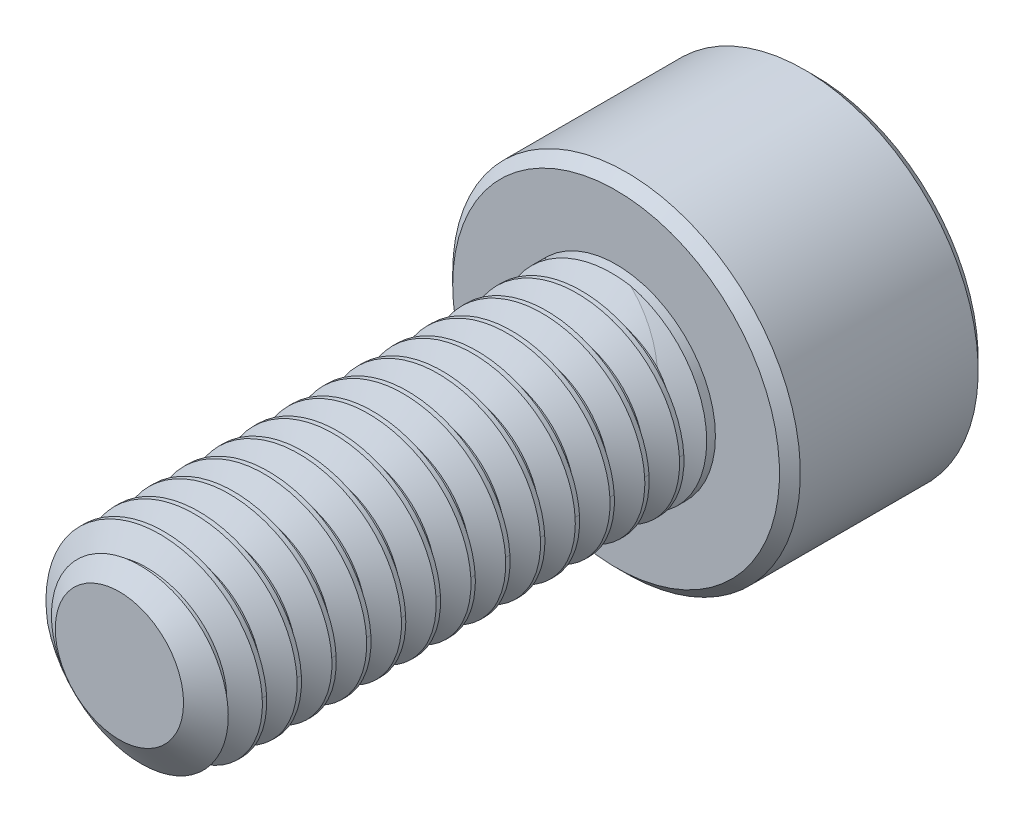
SolidWorks part; units mm, degrees
ref_plane "Front Plane" through (0, 0, 0) normal (0, 0, 1) x (1, 0, 0)
ref_plane "Top Plane" through (0, 0, 0) normal (0, 1, 0) x (1, 0, 0)
ref_plane "Right Plane" through (0, 0, 0) normal (1, 0, 0) x (0, 0, -1)
sketch "Sketch1" plane through (0, 0, 0) normal (0, 0, 1) x (1, 0, 0)
  circle A0 centre (0, 0) radius 2
  dimension "OD" = 4
extrude "Extrude1" add sketch "Sketch1" against normal blind 10
sketch "Sketch2" plane through (0, 0, 0) normal (0, 0, 1) x (1, 0, 0)
  circle A0 centre (0, 0) radius 2 construction
  circle A1 centre (0, 0) radius 2
curve "Helix/Spiral1" pitch 0.7 height 10.7 radius 2 centre (0, 0, 0) axis (0, 0, -1) start towards (0, 1, 0) parameters "pitch"=0.7
sketch "Sketch3" plane through (0, 0, 0) normal (1, 0, 0) x (0, 0, -1)
  line L0 (-0.6125, 2) -> (-0.35, 1.5453)
  line L1 (-0.35, 1.5453) -> (-0.2625, 1.5453)
  line L2 (-0.2625, 1.5453) -> (0, 2)
  line L3 (-0.6125, 2) -> (0, 2)
  line L4 (-0.3063, 2) -> (-0.3063, 1.5453) construction
  line L5 (-0.4813, 1.7727) -> (-0.1313, 1.7727) construction
  line L6 (0, 2) -> (0, -2) construction
  line L7 (0, -2) -> (10, -2) construction
  point P11 (3.15, -2)
  dimension "D1" = 0.0875
  dimension "D2" = 0.35
  dimension "D3" = 60
  dimension "D4" = 3.15
sweep "Cut-Sweep1" cut profiles "Sketch3" path "Helix/Spiral1"
sketch "Sketch4" plane through (0, 0, 0) normal (1, 0, 0) x (0, 0, -1)
  line L0 (0.4962, 2) -> (0, 1.2913)
  line L1 (0, 1.2913) -> (0, 2)
  line L2 (0.4962, 2) -> (0, 2)
  line L3 (-0.6125, 2) -> (0, 2) construction
  line L4 (0, 0) -> (7.0209, 0) construction
  dimension "D1" = 55
  dimension "D2" = 0.254
revolve "Cut-Revolve1" cut sketch "Sketch4" angle 360 about L4
sketch "Sketch5" plane through (0, 0, 0) normal (1, 0, 0) x (0, 0, -1)
  line L0 (10, 0.3311) -> (10, 1.814) construction
  line L1 (10, 2) -> (0.1203, 2)
  line L2 (10, 2) -> (10, 0)
  line L3 (10, 0) -> (0.0001, 0)
  line L4 (0.0001, 1.6698) -> (0.0001, 0)
  line L5 (0.1203, 2) -> (0.0001, 1.6698)
  line L6 (0, 0) -> (9.9695, 0) construction
  point P3 (0.0001, 2)
  point P10 (0.0001, 2)
  dimension "D1" = 0.3302
  dimension "Thread min" = 0.0001
  dimension "D3" = 20
revolve "partially thread" [suppressed] add sketch "Sketch5" angle 360 about L6
sketch "Sketch6" plane through (0, 0, -10) normal (0, 0, -1) x (-1, 0, 0)
  circle A0 centre (0, 0) radius 3.5
  dimension "head dia" = 7
extrude "Extrude2" add sketch "Sketch6" along normal blind 4
sketch "Sketch7" plane through (0, 0, -14) normal (0, 0, -1) x (-1, 0, 0)
  line L1 (0, 1.7321) -> (-1.5, 0.866)
  line L2 (-1.5, 0.866) -> (-1.5, -0.866)
  line L3 (-1.5, -0.866) -> (0, -1.7321)
  line L4 (0, -1.7321) -> (1.5, -0.866)
  line L5 (1.5, -0.866) -> (1.5, 0.866)
  line L6 (1.5, 0.866) -> (0, 1.7321)
  circle A0 centre (0, 0) radius 1.5 construction
  dimension "hex dia" = 3
extrude "Cut-Extrude1" cut sketch "Sketch7" against normal blind 2.25
sketch "Sketch8" plane through (0, 0, -14) normal (0, 0, -1) x (-1, 0, 0)
  circle A0 centre (0, 0) radius 1.7321
extrude "Cut-Extrude2" cut sketch "Sketch8" against normal through all draft 45
chamfer "Chamfer1" distance 0.21 angle 45 2 edges at (-3.5, 0, -14) (-3.5, 0, -10)
sketch "Sketch9" plane through (0, 0, 0) normal (1, 0, 0) x (0, 0, -1)
  line L0 (0, 2) -> (0, -2) construction
  line L1 (3.85, 2) -> (3.85, -2) construction
  dimension "D1" = 3.85
sketch "Sketch10" plane through (0, 0, 0) normal (1, 0, 0) x (0, 0, -1)
  line L0 (10, 2) -> (10, 0)
  line L1 (10, 2) -> (9.825, 2)
  line L2 (9.825, 2) -> (8.9966, 0)
  line L3 (10, 0) -> (8.9966, 0)
  line L4 (10, 3.29) -> (10, -3.29) construction
  dimension "D1" = 22.5
  dimension "D2" = 0.175
revolve "Revolve1" add sketch "Sketch10" angle 360 about L3
equation "\"D3@Helix/Spiral1\" = \"screw length@Extrude1\"+\"pitch@Helix/Spiral1\""
equation "\"D1@Sketch3\" = \"pitch@Helix/Spiral1\"*.125"
equation "\"D2@Sketch3\" = \"pitch@Helix/Spiral1\"*.5"
equation "\"D1@Cut-Extrude1\" = \"hex dia@Sketch7\"*.75"
equation "\"D1@Chamfer1\" = \"head dia@Sketch6\"*.03"
equation "\"D1@Sketch9\" = \"pitch@Helix/Spiral1\"*5.5"
equation "\"D2@Sketch10\" = \"pitch@Helix/Spiral1\"*.25"
equation "\"D4@Sketch3\" = \"pitch@Helix/Spiral1\"*4.50"
